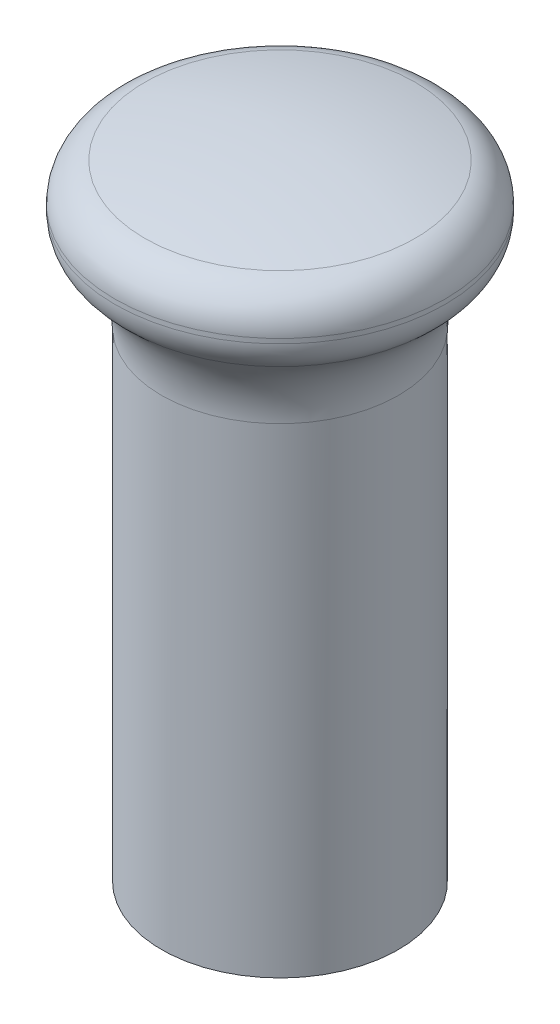
SolidWorks part; units mm, degrees
material "6061-T6 (SS)"
ref_plane "Front Plane" through (0, 0, 0) normal (0, 0, 1) x (1, 0, 0)
ref_plane "Top Plane" through (0, 0, 0) normal (0, 1, 0) x (1, 0, 0)
ref_plane "Right Plane" through (0, 0, 0) normal (1, 0, 0) x (0, 0, -1)
sketch "Sketch1" plane through (0, 0, 0) normal (1, 0, 0) x (0, 0, -1)
  line L0 (0, 25.4) -> (0, 46.4566) construction
  line L2 (4.8966, 14.7066) -> (-5.3865, 14.7066) construction
  line L3 (0, 46.4566) -> (5.4356, 46.4566) construction
  line L4 (5.4356, 46.4566) -> (5.4356, 43.9166) construction
  line L5 (5.4356, 43.9166) -> (3.899, 43.9166)
  line L6 (3.899, 43.9166) -> (3.899, 25.4)
  line L7 (3.899, 25.4) -> (0, 25.4)
  line L8 (0, 25.4) -> (0, 46.4566)
  line L9 (5.4356, 45.6946) -> (5.4356, 43.9166)
  arc A0 (5.4356, 45.6946) -> (0, 46.4566) centre (0, 26.6886) ccw
  dimension "D1" = 31.75
  dimension "D2" = 7.798
  dimension "D3" = 5.4356
  dimension "D4" = 2.54
  dimension "D5" = 0.762
revolve "Revolve1" add sketch "Sketch1" angle 360 about L0
fillet "Fillet1" radius 3.175 1 edges at (0, 43.9166, -3.899)
fillet "Fillet2" radius 1.27 2 edges at (0, 45.6946, -5.4356) (0, 43.9166, -5.4356)
hole_wizard "M7x0.75 Tapped Hole1" positions "Sketch2" profile "Sketch3" tap size "M7X0.75" standard "ANSI Metric"
sketch "Sketch2" plane through (0, 25.4, 0) normal (0, -1, 0) x (-1, 0, 0)
  point P0 (0, 0)
sketch "Sketch3" plane through (0, 25.4, 0) normal (1, 0, 0) x (0, 0, -1)
  line L0 (0, 0) -> (0, 17.8046)
  line L1 (0, 17.8046) -> (3, 16.002)
  line L2 (3, 16.002) -> (3, 0)
  line L5 (3, 0) -> (0, 0)
  line L10 (0, 17.8046) -> (-3, 16.002) construction
  line L11 (0, -6.35) -> (0, 107.95) construction
  dimension "Tap Drill Dia." = 6
  dimension "Tap Drill Depth" = 16.002
  dimension "Drill Angle" = 118
cosmetic thread "Hole Thread1" parameters "D1"=13.97, "D2"=7
sketch "Sketch4" plane through (0, 25.4, 0) normal (0, -1, 0) x (1, 0, 0)
  circle A0 centre (0, 0) radius 3.5
  dimension "D1" = 7
extrude "Cut-Extrude1" cut sketch "Sketch4" against normal blind 2.5
